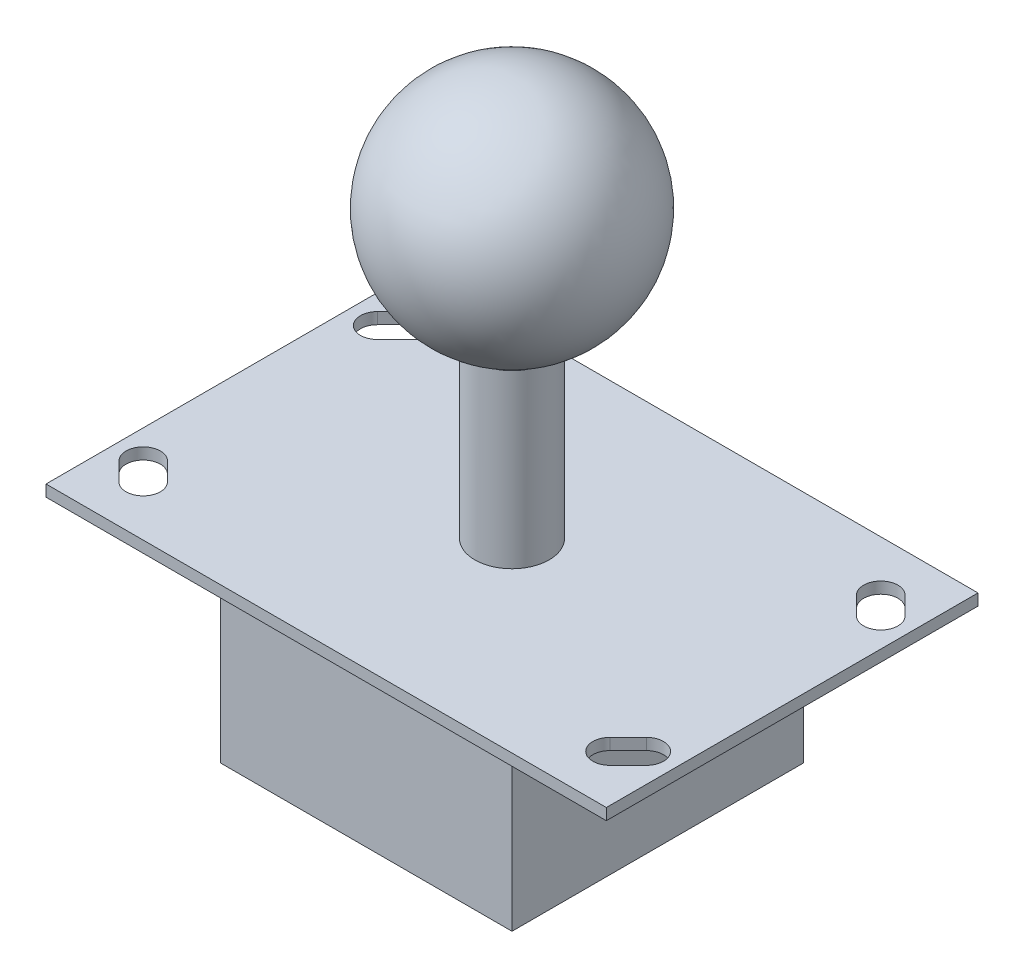
SolidWorks part; units mm, degrees
ref_plane "Front Plane" through (0, 0, 0) normal (0, 0, 1) x (1, 0, 0)
ref_plane "Top Plane" through (0, 0, 0) normal (0, 1, 0) x (1, 0, 0)
ref_plane "Right Plane" through (0, 0, 0) normal (1, 0, 0) x (0, 0, -1)
sketch "Sketch3" plane through (0, 0, 0) normal (0, 1, 0) x (1, 0, 0)
  circle A0 centre (0, 0) radius 6.5
  dimension "D1" = 13
extrude "Boss-Extrude2" add sketch "Sketch3" along normal blind 30
sketch "Sketch4" plane through (0, 0, 0) normal (0, -1, 0) x (-1, 0, 0)
  line L1 (-49, 32.5) -> (49, 32.5)
  line L2 (-49, 32.5) -> (-49, -32.5)
  line L3 (-49, -32.5) -> (49, -32.5)
  line L4 (49, 32.5) -> (49, -32.5)
  point P4 (49, 0)
  point P6 (0, 32.5)
  dimension "D1" = 98
  dimension "D2" = 65
extrude "Boss-Extrude3" add sketch "Sketch4" along normal blind 2
sketch "Sketch5" plane through (0, -2, 0) normal (0, -1, 0) x (1, 0, 0)
  line L1 (-25.5, 25.5) -> (25.5, 25.5)
  line L2 (-25.5, 25.5) -> (-25.5, -25.5)
  line L3 (-25.5, -25.5) -> (25.5, -25.5)
  line L4 (25.5, 25.5) -> (25.5, -25.5)
  point P4 (0, 25.5)
  point P6 (25.5, 0)
  dimension "D1" = 51
  dimension "D2" = 51
extrude "Boss-Extrude4" add sketch "Sketch5" along normal blind 32
sketch "Sketch7" plane through (0, 0, 0) normal (0, 1, 0) x (1, 0, 0)
  line L0 (-46.1213, 22.6213) -> (-42.9393, 25.8033)
  line L1 (-41.8787, 18.3787) -> (-38.6967, 21.5607)
  line L2 (-49, -32.5) -> (-49, 32.5) construction
  line L3 (-49, 32.5) -> (49, 32.5) construction
  line L4 (-49, 0) -> (49, 0) construction
  line L5 (49, 32.5) -> (49, -32.5) construction
  line L6 (0, 32.5) -> (0, -32.5) construction
  line L7 (49, -32.5) -> (-49, -32.5) construction
  line L8 (-46.1213, -22.6213) -> (-42.9393, -25.8033)
  line L9 (-41.8787, -18.3787) -> (-38.6967, -21.5607)
  line L10 (41.8787, -18.3787) -> (38.6967, -21.5607)
  line L11 (46.1213, -22.6213) -> (42.9393, -25.8033)
  line L12 (46.1213, 22.6213) -> (42.9393, 25.8033)
  line L13 (41.8787, 18.3787) -> (38.6967, 21.5607)
  arc A0 (-38.6967, 21.5607) -> (-42.9393, 25.8033) centre (-40.818, 23.682) ccw
  arc A1 (-46.1213, 22.6213) -> (-41.8787, 18.3787) centre (-44, 20.5) ccw
  arc A2 (-38.6967, -21.5607) -> (-42.9393, -25.8033) centre (-40.818, -23.682) cw
  arc A3 (-46.1213, -22.6213) -> (-41.8787, -18.3787) centre (-44, -20.5) cw
  arc A4 (38.6967, -21.5607) -> (42.9393, -25.8033) centre (40.818, -23.682) ccw
  arc A5 (46.1213, -22.6213) -> (41.8787, -18.3787) centre (44, -20.5) ccw
  arc A6 (38.6967, 21.5607) -> (42.9393, 25.8033) centre (40.818, 23.682) cw
  arc A7 (46.1213, 22.6213) -> (41.8787, 18.3787) centre (44, 20.5) cw
  dimension "D1" = 6
  dimension "D2" = 4.5
  dimension "D3" = 5
  dimension "D4" = 12
  dimension "D5" = 4.5
  dimension "D6" = 45
extrude "Cut-Extrude1" cut sketch "Sketch7" against normal through all
sketch3d "3DSketch1"
  line L0 (0, 30, 0) -> (0, 70, 0) construction
  line L1 (0, 30, 0) -> (0, 0, 0) construction
  line L2 (0, 70, 0) -> (0, 30, 0)
  arc A0 (0, 70, 0) -> (0, 30, 0) centre (0, 50, 0) ccw
  point P6 (0, 50, 20)
  dimension "D1" = 40
  dimension "D2" = 20
revolve "Revolve3" add sketch "3DSketch1" angle 360 about L0
